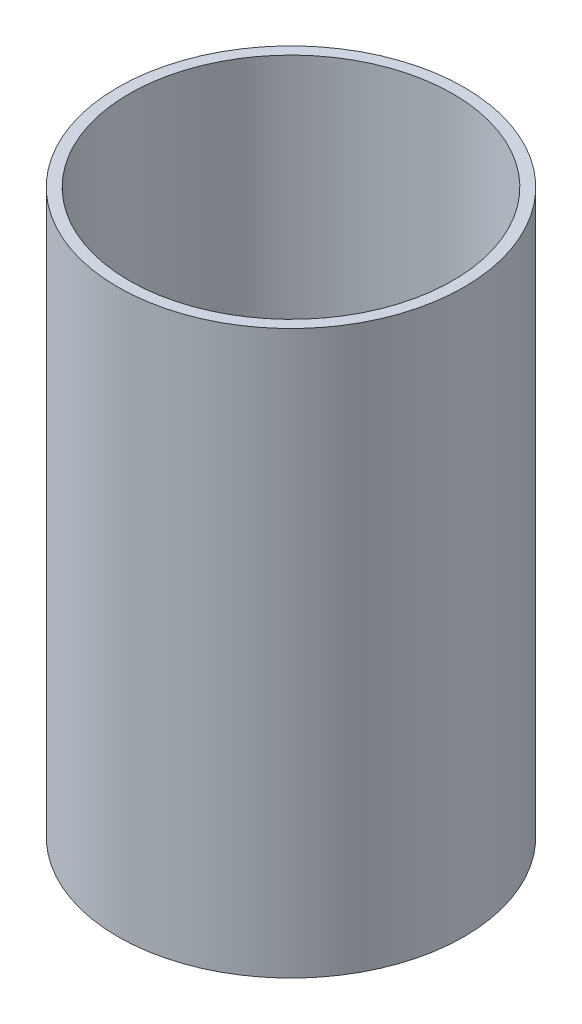
SolidWorks part; units mm, degrees
ref_plane "Front Plane" through (0, 0, 0) normal (0, 0, 1) x (1, 0, 0)
ref_plane "Top Plane" through (0, 0, 0) normal (0, 1, 0) x (1, 0, 0)
ref_plane "Right Plane" through (0, 0, 0) normal (1, 0, 0) x (0, 0, -1)
sketch "Sketch1" plane through (0, 0, 0) normal (0, 1, 0) x (1, 0, 0)
  circle A0 centre (0, 0) radius 23.749
  circle A1 centre (0, 0) radius 25.4
  dimension "D1" = 47.498
  dimension "D2" = 1.651
extrude "Boss-Extrude1" add sketch "Sketch1" along normal blind 82.55
